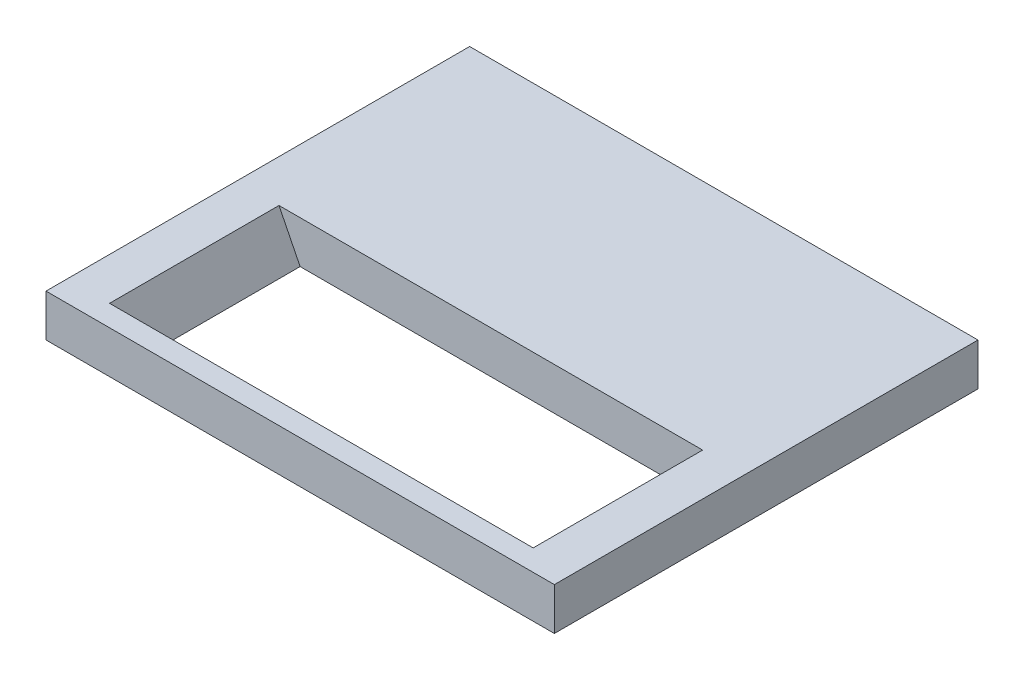
SolidWorks part; units mm, degrees
ref_plane "Front Plane" through (0, 0, 0) normal (0, 0, 1) x (1, 0, 0)
ref_plane "Top Plane" through (0, 0, 0) normal (0, 1, 0) x (1, 0, 0)
ref_plane "Right Plane" through (0, 0, 0) normal (1, 0, 0) x (0, 0, -1)
sketch "Sketch1" plane through (0, 0, 0) normal (0, 1, 0) x (1, 0, 0)
  line L0 (0, 50) -> (0, 32.1573)
  line L1 (-60, 50) -> (60, 50)
  line L2 (-60, 50) -> (-60, -50)
  line L3 (-60, -50) -> (60, -50)
  line L4 (60, 50) -> (60, -50)
  line L5 (-60, 50) -> (-60, 0)
  line L6 (-60, 25) -> (-50, 25)
  line L7 (-60, 50) -> (-60, 40)
  line L8 (-58, 28) -> (-52, 28)
  line L9 (-58, 28) -> (-58, 22)
  line L10 (-58, 22) -> (-52, 22)
  line L11 (-52, 28) -> (-52, 22)
  line L12 (-58, 28) -> (-52, 22) construction
  line L13 (-58, 22) -> (-52, 28) construction
  line L14 (-60, 45) -> (-50, 45)
  line L15 (-60, 0) -> (-60, 10)
  line L16 (-60, 5) -> (-50, 5)
  line L17 (-60, 5) -> (-60, 2)
  line L18 (-58, 2) -> (-52, 2)
  line L19 (-60, 45) -> (-60, 48)
  line L20 (-58, 8) -> (-52, 8)
  line L21 (-58, 8) -> (-58, 2)
  line L22 (-58, 2) -> (-52, 2)
  line L23 (-52, 8) -> (-52, 2)
  line L24 (-58, 8) -> (-52, 2) construction
  line L25 (-58, 2) -> (-52, 8) construction
  line L26 (58, 22) -> (52, 22)
  line L27 (-52, 42) -> (-58, 42)
  line L28 (-52, 42) -> (-52, 48)
  line L29 (-52, 48) -> (-58, 48)
  line L30 (-58, 42) -> (-58, 48)
  line L31 (-52, 42) -> (-58, 48) construction
  line L32 (-52, 48) -> (-58, 42) construction
  line L33 (58, 2) -> (52, 2)
  line L34 (52, 8) -> (52, 2)
  line L35 (58, 8) -> (52, 8)
  line L36 (58, 8) -> (58, 2)
  line L37 (52, 48) -> (58, 48)
  line L38 (52, 42) -> (52, 48)
  line L39 (52, 42) -> (58, 42)
  line L40 (58, 42) -> (58, 48)
  line L41 (-60, 0) -> (-60, -5)
  line L42 (52, 28) -> (52, 22)
  line L43 (-60, -2.5) -> (-60, -1)
  line L44 (58, 28) -> (52, 28)
  line L45 (58, 28) -> (58, 22)
  line L46 (-60, -2.5) -> (-57.5, -2.5)
  line L47 (-60, -50) -> (-60, 0)
  line L48 (-59, -4) -> (-56, -4)
  line L49 (-59, -4) -> (-59, -1)
  line L50 (-59, -1) -> (-56, -1)
  line L51 (-56, -4) -> (-56, -1)
  line L52 (-60, -50) -> (-60, 0)
  line L53 (-55, -5) -> (-60, -5)
  line L54 (-55, -5) -> (-55, 0)
  line L55 (-59, -49) -> (-56, -49)
  line L56 (-56, -46) -> (-56, -49)
  line L57 (-59, -46) -> (-56, -46)
  line L58 (-59, -46) -> (-59, -49)
  line L59 (-55, 0) -> (-60, 0)
  line L60 (59, -46) -> (59, -49)
  line L61 (59, -46) -> (56, -46)
  line L62 (56, -46) -> (56, -49)
  line L63 (59, -49) -> (56, -49)
  line L64 (59, -1) -> (56, -1)
  line L65 (56, -4) -> (56, -1)
  line L66 (59, -4) -> (56, -4)
  line L67 (59, -4) -> (59, -1)
  line L68 (-50, 50) -> (-50, -50)
  line L69 (50, 50) -> (50, -50)
  line L70 (-60, -5) -> (-60, 0)
  line L71 (-55, -5) -> (-60, 0) construction
  line L72 (-55, 0) -> (-60, -5) construction
  line L73 (-60, -50) -> (-60, -23.4585)
  line L74 (-60, 0) -> (-60, -50)
  line L75 (-60, -50) -> (-60, -47.5)
  line L76 (0, -50) -> (0, -45)
  line L77 (-55, -45) -> (-60, -45)
  line L78 (-55, -45) -> (-55, -50)
  line L79 (-55, -50) -> (-60, -50)
  line L80 (-60, -45) -> (-60, -50)
  line L81 (-55, -45) -> (-60, -50) construction
  line L82 (-55, -50) -> (-60, -45) construction
  line L83 (55, -50) -> (60, -50)
  line L84 (60, -45) -> (60, -50)
  line L85 (55, -45) -> (60, -45)
  line L86 (55, -45) -> (55, -50)
  line L87 (55, 0) -> (60, 0)
  line L88 (60, -5) -> (60, 0)
  line L89 (55, -5) -> (60, -5)
  line L90 (55, -5) -> (55, 0)
  line L91 (-60, 25) -> (-60, 20)
  line L92 (-60, 20) -> (-55, 20)
  line L93 (50, 20) -> (60, 20)
  line L94 (-50, 30) -> (-60, 30)
  line L95 (-50, 30) -> (-50, 20)
  line L96 (-50, 20) -> (-60, 20)
  line L97 (-60, 30) -> (-60, 20)
  line L98 (-50, 30) -> (-60, 20) construction
  line L99 (-50, 20) -> (-60, 30) construction
  line L100 (60, 30) -> (60, 20)
  line L101 (50, 30) -> (60, 30)
  line L102 (50, 30) -> (50, 20)
  line L103 (52, 48) -> (58, 48)
  line L104 (58, 42) -> (58, 48)
  line L105 (52, 42) -> (52, 48)
  line L106 (52, 42) -> (58, 42)
  line L107 (52, 28) -> (58, 28)
  line L108 (58, 22) -> (58, 28)
  line L109 (52, 22) -> (52, 28)
  line L110 (58, 22) -> (52, 22)
  point P0 (0, 0)
  point P10 (-55, 25)
  point P21 (-55, 5)
  point P24 (-55, 45)
  point P49 (-57.5, -47.5)
  point P51 (-57.5, -2.5)
  point P90 (-55, 25)
  dimension "D1" = 120
  dimension "D2" = 100
  dimension "D3" = 6
  dimension "D4" = 6
  dimension "D5" = 6
extrude "Boss-Extrude1" add sketch "Sketch1" against normal blind 10 contours L69 L1 L68 L3 | L1 L69 L3 L4 L60 L63 L62 L61 L35 L36 L33 L34 L40 L39 L38 L37 L67 L66 L65 L64 | L36 L35 L34 L33 | L66 L67 L64 L65 | L63 L60 L61 L62 | L68 L16 L23 L18 L21 L15 L2 L41 L3 L58 L57 L56 L55 L51 L48 L49 L50 | L57 L58 L55 L56 | L48 L51 L50 L49 | L68 L6 L11 L10 L9 L5 L2 L16 L21 L20 L23 | L23 L20 L21 L16 | L23 L16 L21 L18 | L11 L6 L9 L10 | L11 L8 L9 L6 | L68 L14 L28 L27 L30 L7 L5 L6 L9 L8 L11 | L68 L1 L2 L7 L14 L30 L29 L28 | L30 L14 L28 L29 | L30 L27 L28 L14 | L96 L68 L6 L11 L10 L9 L5 L92 | L68 L94 L2 L6 L9 L8 L11 | L54 L59 L2 L41 L49 L50 L51 L48 L53 | L78 L77 L74 L3 L58 L57 L56 L55 | L85 L86 L3 L4 L60 L63 L62 L61 | L90 L89 L4 L87 L67 L66 L65 L64 | L45 L44 L42 L26 | L39 L40 L37 L38 | L69 L101 L4 L1 L40 L39 L38 L37 | L101 L69 L93 L4 L44 L45 L26 L42 | L26 L42 L44 L45 | L95 L94 L97 L96 | L9 L8 L11 L10 | L54 L53 L70 L59 | L78 L77 L80 L79 | L84 L85 L86 L83 | L87 L88 L89 L90 | L2 L1 L4 L3 | L38 L37 L40 L39 region at (-55, 0, -48.0625) region at (0, 0, 0) region at (-55, 0, -36.6818) region at (55, 0, -38.9024) region at (-55, 0, -43.5) region at (-55, 0, -46.5) region at (-55, 0, -28.0625) region at (55, 0, -29.8586) region at (-55, 0, -21.9375) region at (54.7964, 0, 15.3583) region at (-55, 0, -23.5) region at (-55, 0, -26.5) region at (-55, 0, -13.3182) region at (-54.7407, 0, 23.2116) region at (59.9293, 0, 2.5) region at (55.0707, 0, 47.5) region at (-55, 0, -3.5) region at (-55, 0, -6.5) region at (-57.5, 0, 49.9293) region at (-58.9576, 0, 1.75) region at (-57.5, 0, 0.0707) region at (55, 0, -25) region at (55, 0, -5) region at (55, 0, -45) region at (-57.5, 0, 47.5) region at (57.5, 0, 47.5) region at (57.5, 0, 2.5)
sketch "Sketch2" plane through (0, -10, 0) normal (0, -1, 0) x (1, 0, 0)
  line L0 (-50, 50) -> (50, 50)
  line L1 (50, 50) -> (50, -50)
  line L2 (50, -50) -> (-50, -50)
  line L3 (-50, -50) -> (-50, 50)
  line L4 (-50, 50) -> (-50, 45)
  line L5 (-50, 45) -> (-45, 45)
  line L6 (-45, 45) -> (-45, 50)
  line L7 (-45, 50) -> (-50, 50)
  line L8 (-50, 50) -> (-50, 47.5)
  line L9 (-50, 50) -> (-47.5, 50)
  line L10 (-50, 47.5) -> (-47.5, 47.5)
  line L11 (-47.5, 47.5) -> (-47.5, 49)
  line L12 (-47.5, 47.5) -> (-46, 47.5)
  line L13 (-50, -5) -> (-45, -5)
  line L14 (-49, 46) -> (-46, 46)
  line L15 (-49, 46) -> (-49, 49)
  line L16 (-49, 49) -> (-46, 49)
  line L17 (-46, 46) -> (-46, 49)
  line L18 (-49, 46) -> (-46, 49) construction
  line L19 (-49, 49) -> (-46, 46) construction
  line L20 (-50, 0) -> (-40, 0)
  line L21 (-40, 0) -> (-40, -10)
  line L22 (-40, -10) -> (-50, -10)
  line L23 (-50, -10) -> (-50, 0)
  line L24 (-45, -5) -> (-45, -2)
  line L25 (-45, -5) -> (-42, -5)
  line L26 (0, -50) -> (0, -29.8037)
  line L27 (-48, -8) -> (-42, -8)
  line L28 (-48, -8) -> (-48, -2)
  line L29 (-48, -2) -> (-42, -2)
  line L30 (-42, -8) -> (-42, -2)
  line L31 (-48, -8) -> (-42, -2) construction
  line L32 (-48, -2) -> (-42, -8) construction
  line L33 (-50, -25) -> (-32.9312, -25)
  line L34 (-48, -48) -> (-42, -48)
  line L35 (-42, -42) -> (-42, -48)
  line L36 (-48, -42) -> (-42, -42)
  line L37 (-48, -42) -> (-48, -48)
  line L38 (48, -42) -> (48, -48)
  line L39 (48, -42) -> (42, -42)
  line L40 (42, -42) -> (42, -48)
  line L41 (48, -48) -> (42, -48)
  line L42 (48, -2) -> (42, -2)
  line L43 (42, -8) -> (42, -2)
  line L44 (48, -8) -> (42, -8)
  line L45 (48, -8) -> (48, -2)
  line L46 (49, 49) -> (46, 49)
  line L47 (46, 46) -> (46, 49)
  line L48 (49, 46) -> (46, 46)
  line L49 (49, 46) -> (49, 49)
  line L50 (50, 50) -> (50, 0)
  line L51 (50, 0) -> (50, 25)
  line L52 (50, 25) -> (29.5204, 25)
  line L53 (-49, 1) -> (-46, 1)
  line L54 (-46, 4) -> (-46, 1)
  line L55 (-49, 4) -> (-46, 4)
  line L56 (-49, 4) -> (-49, 1)
  line L57 (49, 4) -> (49, 1)
  line L58 (49, 4) -> (46, 4)
  line L59 (46, 4) -> (46, 1)
  line L60 (49, 1) -> (46, 1)
  line L61 (-50, -5) -> (-50, -25)
  line L62 (-50, -15) -> (-38.6156, -15)
  line L63 (-48, -28) -> (-42, -28)
  line L64 (-42, -22) -> (-42, -28)
  line L65 (-48, -22) -> (-42, -22)
  line L66 (-48, -22) -> (-48, -28)
  line L67 (48, -22) -> (48, -28)
  line L68 (48, -22) -> (42, -22)
  line L69 (42, -22) -> (42, -28)
  line L70 (48, -28) -> (42, -28)
  line L71 (-45, 5) -> (-40, 5)
  line L72 (45, 5) -> (-45, 5)
  line L73 (45, 5) -> (45, 45)
  line L74 (45, 45) -> (-45, 45)
  line L75 (-45, 5) -> (-45, 45)
  line L76 (45, 5) -> (-45, 45) construction
  line L77 (45, 45) -> (-45, 5) construction
  point P78 (0, 25)
extrude "Cut-Extrude1" cut sketch "Sketch2" against normal blind 10 contours L75 L72 L73 L74 region at (0, -10, 25)
extrude "Cut-Extrude2" cut sketch "Sketch2<3>" against normal blind 6 contours L48 L49 L46 L47 | L55 L56 L53 L54 | L60 L57 L58 L59 | L70 L67 L68 L69 | L14 L17 L16 L15 | L63 L64 L65 L66 region at (47.5, -10, 47.5) region at (-47.5, -10, 2.5) region at (47.5, -10, 2.5) region at (45, -10, -25)
sketch "Sketch2<3>" plane through (0, -10, 0) normal (0, -1, 0) x (1, 0, 0) same geometry as "Sketch2"
sketch "Sketch3" plane through (0, 0, 0) normal (0, 1, 0) x (1, 0, 0)
  line L0 (-50, -5) -> (-50, -45)
  line L1 (50, -5) -> (50, -45)
  line L2 (-60, -5) -> (-50, -5)
  line L3 (-50, -45) -> (-60, -45)
  line L4 (-60, 50) -> (-60, -50) construction
  line L5 (50, -45) -> (60, -45)
  line L6 (60, 50) -> (60, -50) construction
  line L7 (50, -5) -> (60, -5)
  line L8 (-50, -5) -> (-45, -5)
  line L9 (-45, -5) -> (-45, -45)
  line L10 (-45, -45) -> (-50, -45)
  line L11 (45, -5) -> (45, -45)
  line L12 (45, -45) -> (50, -45)
  line L13 (45, -5) -> (50, -5)
chamfer "Chamfer2" distance 5 angle 63.5 1 edges at (-45, 0, 25) first distance on face at (0, 0, 0)
chamfer "Chamfer3" distance 10 angle 26.565 1 edges at (45, 0, 25) first distance on face at (45, -5, 25)
